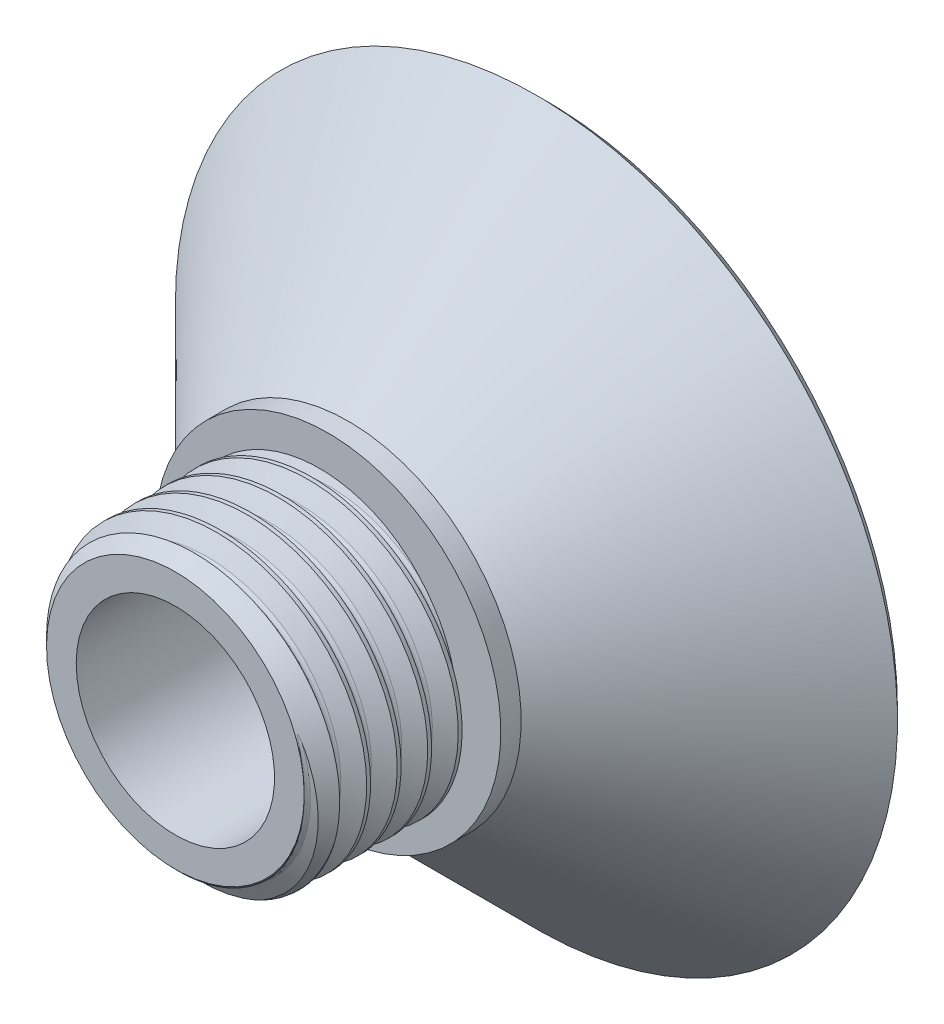
SolidWorks part; units mm, degrees
ref_plane "Front Plane" through (0, 0, 0) normal (0, 0, 1) x (1, 0, 0)
ref_plane "Top Plane" through (0, 0, 0) normal (0, 1, 0) x (1, 0, 0)
ref_plane "Right Plane" through (0, 0, 0) normal (1, 0, 0) x (0, 0, -1)
sketch "Sketch1" plane through (0, 0, 0) normal (1, 0, 0) x (0, 0, -1)
  line L1 (0, 0) -> (-153.1218, 0) construction
  line L2 (0, 2.85) -> (0, 35.5)
  line L3 (0, 35.5) -> (-1, 35.5)
  line L4 (-1, 35.5) -> (-19.5, 17)
  line L5 (-19.5, 17) -> (-21.5, 17)
  line L6 (-21.5, 17) -> (-21.5, 12.67)
  line L7 (-21.5, 12.67) -> (-36.5, 12.67)
  line L8 (-36.5, 12.67) -> (-36.5, 9.75)
  line L9 (-36.5, 9.75) -> (-3.3, 9.75)
  line L10 (-3.3, 9.75) -> (-3.3, 2.85)
  line L11 (-3.3, 2.85) -> (0, 2.85)
  dimension "D1" = 45
  dimension "D3" = 34
  dimension "D4" = 1
  dimension "D5" = 25.34
  dimension "D6" = 2
  dimension "D7" = 15
  dimension "D8" = 19.5
  dimension "D9" = 5.7
  dimension "D10" = 3.3
  dimension "D11" = 21.5
revolve "Revolve1" add sketch "Sketch1" angle 360 about L1
sketch "Sketch2" plane through (0, 0, 21.5) normal (0, 0, 1) x (1, 0, 0)
  circle A0 centre (0, 0) radius 12.67 construction
  circle A1 centre (0, 0) radius 12.67
curve "Helix/Spiral1" pitch 3 height 18 radius 12.67 centre (0, 0, 21.5) axis (0, 0, 1) start towards (1, 0, 0)
sketch "Sketch4" plane through (0, 0, 0) normal (0, 1, 0) x (1, 0, 0)
  line L0 (12.886, -36.1259) -> (14.5, -35.194)
  line L1 (14.5, -35.194) -> (14.5, -34.816)
  line L2 (12.67, -36.5) -> (12.67, -33.51)
  line L3 (-12.67, -36.5) -> (12.67, -36.5) construction
  line L4 (14.5, -35.005) -> (12.67, -35.005) construction
  line L5 (12.886, -33.8841) -> (14.5, -34.816)
  arc A0 (12.886, -36.1259) -> (12.67, -36.5) centre (13.102, -36.5) ccw
  arc A1 (12.886, -33.8841) -> (12.67, -33.51) centre (13.102, -33.51) cw
  spline S0 degree 3 poles (12.67, -21.5) (12.67, -21.5621) (12.0103, -21.6877) (9.1923, -21.875) (4.9748, -22.0625) (0, -22.25) (-4.9748, -22.4375) (-9.1923, -22.625) (-12.0103, -22.8125) (-12.9999, -23) (-12.0103, -23.1875) (-9.1923, -23.375) (-4.9748, -23.5625) (0, -23.75) (4.9748, -23.9375) (9.1923, -24.125) (12.0103, -24.3125) (12.9999, -24.5) (12.0103, -24.6875) (9.1923, -24.875) (4.9748, -25.0625) (0, -25.25) (-4.9748, -25.4375) (-9.1923, -25.625) (-12.0103, -25.8125) (-12.9999, -26) (-12.0103, -26.1875) (-9.1923, -26.375) (-4.9748, -26.5625) (0, -26.75) (4.9748, -26.9375) (9.1923, -27.125) (12.0103, -27.3125) (12.9999, -27.5) (12.0103, -27.6875) (9.1923, -27.875) (4.9748, -28.0625) (0, -28.25) (-4.9748, -28.4375) (-9.1923, -28.625) (-12.0103, -28.8125) (-12.9999, -29) (-12.0103, -29.1875) (-9.1923, -29.375) (-4.9748, -29.5625) (0, -29.75) (4.9748, -29.9375) (9.1923, -30.125) (12.0103, -30.3125) (12.9999, -30.5) (12.0103, -30.6875) (9.1923, -30.875) (4.9748, -31.0625) (0, -31.25) (-4.9748, -31.4375) (-9.1923, -31.625) (-12.0103, -31.8125) (-12.9999, -32) (-12.0103, -32.1875) (-9.1923, -32.375) (-4.9748, -32.5625) (0, -32.75) (4.9748, -32.9375) (9.1923, -33.125) (12.0103, -33.3125) (12.9999, -33.5) (12.0103, -33.6875) (9.1923, -33.875) (4.9748, -34.0625) (0, -34.25) (-4.9748, -34.4375) (-9.1923, -34.625) (-12.0103, -34.8125) (-12.9999, -35) (-12.0103, -35.1875) (-9.1923, -35.375) (-4.9748, -35.5625) (0, -35.75) (4.9748, -35.9375) (9.1923, -36.125) (12.0103, -36.3125) (12.9999, -36.5) (12.0103, -36.6875) (9.1923, -36.875) (4.9748, -37.0625) (0, -37.25) (-4.9748, -37.4375) (-9.1923, -37.625) (-12.0103, -37.8125) (-12.9999, -38) (-12.0103, -38.1875) (-9.1923, -38.375) (-4.9748, -38.5625) (0, -38.75) (4.9748, -38.9375) (9.1923, -39.125) (12.0103, -39.3123) (12.67, -39.4379) (12.67, -39.5) knots 0 0 0 0 0.010417 0.020833 0.03125 0.041667 0.052083 0.0625 0.072917 0.083333 0.09375 0.104167 0.114583 0.125 0.135417 0.145833 0.15625 0.166667 0.177083 0.1875 0.197917 0.208333 0.21875 0.229167 0.239583 0.25 0.260417 0.270833 0.28125 0.291667 0.302083 0.3125 0.322917 0.333333 0.34375 0.354167 0.364583 0.375 0.385417 0.395833 0.40625 0.416667 0.427083 0.4375 0.447917 0.458333 0.46875 0.479167 0.489583 0.5 0.510417 0.520833 0.53125 0.541667 0.552083 0.5625 0.572917 0.583333 0.59375 0.604167 0.614583 0.625 0.635417 0.645833 0.65625 0.666667 0.677083 0.6875 0.697917 0.708333 0.71875 0.729167 0.739583 0.75 0.760417 0.770833 0.78125 0.791667 0.802083 0.8125 0.822917 0.833333 0.84375 0.854167 0.864583 0.875 0.885417 0.895833 0.90625 0.916667 0.927083 0.9375 0.947917 0.958333 0.96875 0.979167 0.989583 1 1 1 1 construction
  dimension "D2" = 0.432
  dimension "D1" = 1.83
  dimension "D3" = 60
  dimension "D4" = 2.99
sweep "Sweep5" add profiles "Sketch4" path "Helix/Spiral1"
sketch "Sketch11" plane through (0, 0, 0) normal (0, 1, 0) x (1, 0, 0)
  line L0 (0, 0) -> (0, -46.1811) construction
  line L1 (17.2033, -36.5) -> (-17.0232, -36.5)
  line L2 (-17, -21.5) -> (17, -21.5) construction
  dimension "D1" = 15
extrude "Cut-Extrude1" cut sketch "Sketch11" against normal through all and the other way through all
sketch "Sketch12" plane through (0, 0, 0) normal (0, 1, 0) x (1, 0, 0)
  line L0 (0, 0) -> (0, -42.7931) construction
  line L1 (12.67, -36.5) -> (15.17, -34)
  line L2 (15.17, -34) -> (15.17, -36.5)
  line L3 (15.17, -36.5) -> (12.67, -36.5)
  dimension "D1" = 45
  dimension "D2" = 2.5
revolve "Cut-Revolve1" cut sketch "Sketch12" angle 360 about L0
chamfer "Chamfer1" distance 1 angle 45 1 edges at (-35.5, 0, 0)
